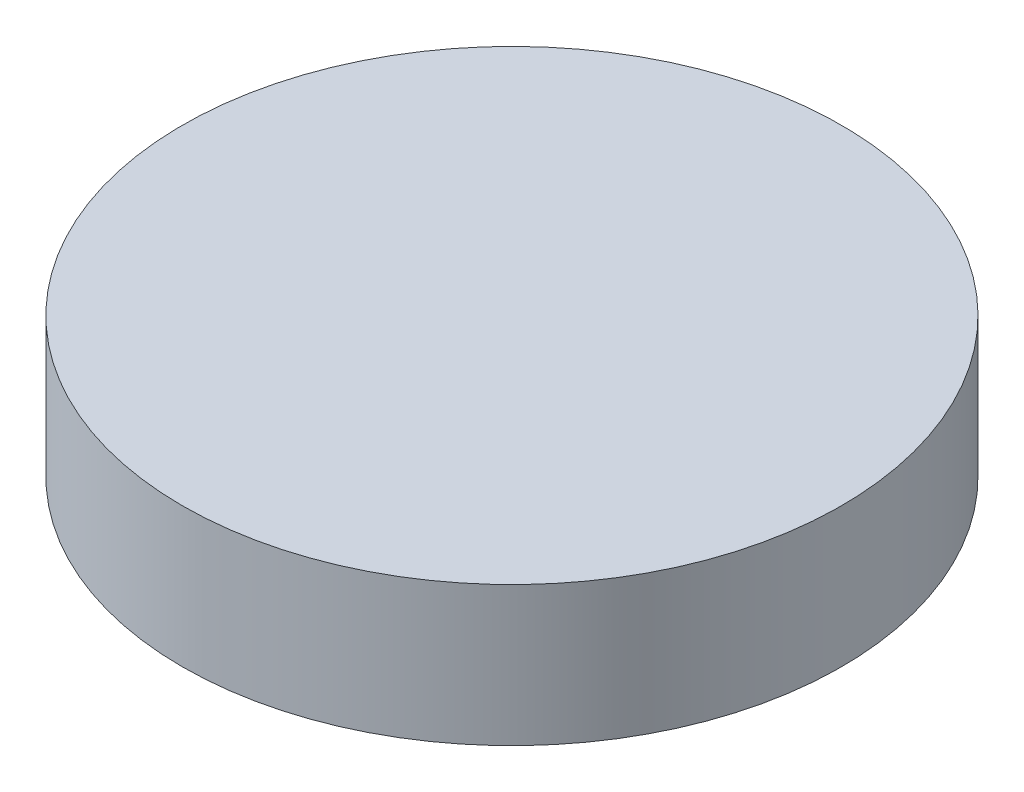
SolidWorks part; units mm, degrees
ref_plane "Front Plane" through (0, 0, 0) normal (0, 0, 1) x (1, 0, 0)
ref_plane "Top Plane" through (0, 0, 0) normal (0, 1, 0) x (1, 0, 0)
ref_plane "Right Plane" through (0, 0, 0) normal (1, 0, 0) x (0, 0, -1)
sketch "Sketch1" plane through (0, 0, 0) normal (0, 1, 0) x (1, 0, 0)
  circle A0 centre (0, 0) radius 3
  dimension "D1" = 6
extrude "Boss-Extrude1" add sketch "Sketch1" along normal blind 1.27
